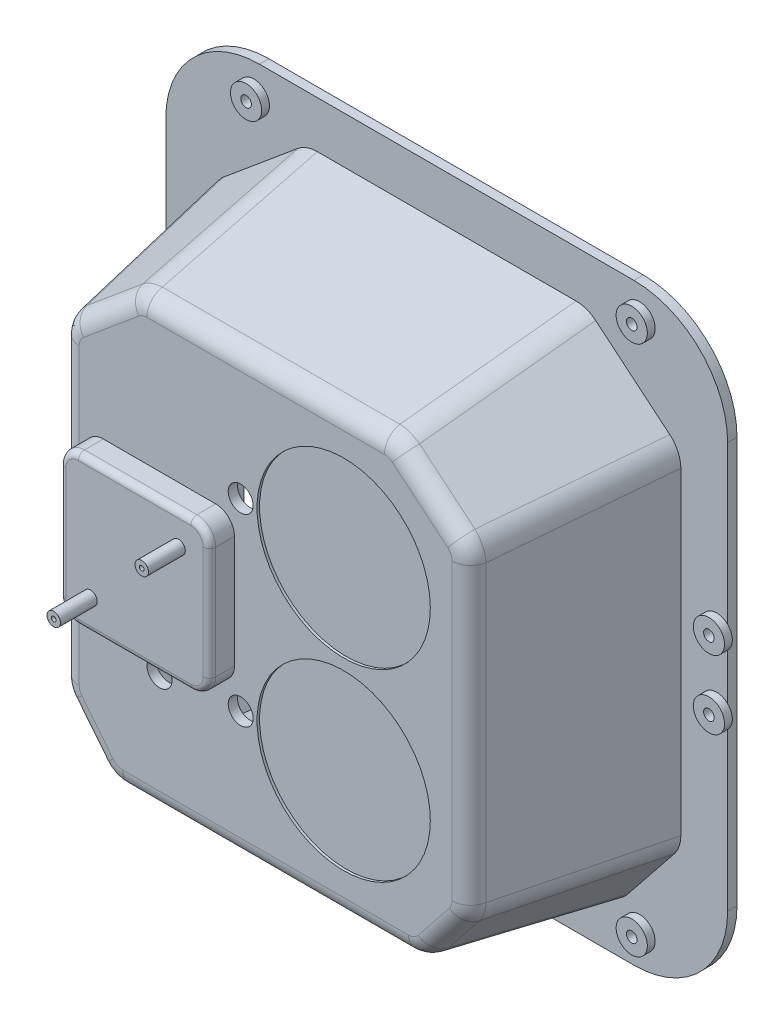
SolidWorks part; units mm, degrees
ref_plane "Front Plane" through (0, 0, 0) normal (0, 0, 1) x (1, 0, 0)
ref_plane "Top Plane" through (0, 0, 0) normal (0, 1, 0) x (1, 0, 0)
ref_plane "Right Plane" through (0, 0, 0) normal (1, 0, 0) x (0, 0, -1)
sketch "SK_Brim_180x190" plane through (0, 0, 0) normal (0, 0, 1) x (1, 0, 0)
  line L1 (-90, -95) -> (90, -95)
  line L2 (-90, -95) -> (-90, 95)
  line L3 (-90, 95) -> (90, 95)
  line L4 (90, -95) -> (90, 95)
  line L5 (-72, -77) -> (72, -77)
  line L6 (-72, -77) -> (-72, 77)
  line L7 (-72, 77) -> (72, 77)
  line L8 (72, -77) -> (72, 77)
extrude "Board_Mount_Brim_3mm" add sketch "SK_Brim_180x190" along normal blind 3
fillet "Brim_Outer_R30" radius 30 4 edges at (-90, 95, 1.5) (90, 95, 1.5) (90, -95, 1.5) (-90, -95, 1.5)
fillet "Brim_Inner_R10" radius 10 4 edges at (-72, 77, 1.5) (72, 77, 1.5) (72, -77, 1.5) (-72, -77, 1.5)
sketch "SK_Cockpit_Octagon" plane through (0, 0, 3) normal (0, 0, 1) x (1, 0, 0)
  line L0 (-55, -80) -> (55, -80)
  line L1 (55, -80) -> (75, -55)
  line L2 (75, -55) -> (75, 55)
  line L3 (75, 55) -> (45, 80)
  line L4 (45, 80) -> (-45, 80)
  line L5 (-45, 80) -> (-75, 55)
  line L6 (-75, 55) -> (-75, -55)
  line L7 (-75, -55) -> (-55, -80)
extrude "Cockpit_Canopy_Draft10deg" add sketch "SK_Cockpit_Octagon" along normal blind 58 draft 10
fillet "Canopy_Corners_R10" radius 10 8 edges at (-69.8865, -53.2063, 32) (-69.8865, 52.605, 32) (-43.1487, 74.8865, 32) (43.1487, 74.8865, 32) (69.8865, 52.605, 32) (69.8865, -53.2063, 32) (52.5423, -74.8865, 32) (-52.5423, -74.8865, 32)
fillet "Canopy_Roof_R6" radius 6 16 edges at (-57.8283, -60.0936, 61) (0, -69.773, 61) (57.8283, -60.0936, 61) (64.773, -1.1804, 61) (52.633, 60.3267, 61) (0, 69.773, 61) (-52.633, 60.3267, 61) (-64.773, -1.1804, 61) (-49.6183, -68.8027, 61) (49.6183, -68.8027, 61) (64.2184, -51.218, 61) (63.8447, 49.7752, 61) (41.0846, 69.1854, 61) (-41.0846, 69.1854, 61) (-63.8447, 49.7752, 61) (-64.2184, -51.218, 61)
sketch "SK_Symmetric_Cavity" plane through (0, 0, 0) normal (0, 0, -1) x (-1, 0, 0)
  line L0 (-53, -77) -> (53, -77)
  line L1 (57.3444, -77) -> (-57.3444, -77) construction
  line L2 (53, -77) -> (72, -52)
  line L3 (72, 57.4649) -> (72, -58.75) construction
  line L4 (72, -52) -> (72, 52)
  line L5 (72, 52) -> (43, 77)
  line L6 (-62, 77) -> (62, 77) construction
  line L7 (43, 77) -> (-43, 77)
  line L8 (-43, 77) -> (-72, 52)
  line L9 (-72, -67) -> (-72, 67) construction
  line L10 (-72, 52) -> (-72, -52)
  line L11 (-72, -52) -> (-53, -77)
extrude "Symmetric_Electronics_Cavity_58H" cut sketch "SK_Symmetric_Cavity" against normal blind 58 draft 10
sketch "Sketch7" plane through (0, 0, 61) normal (0, 0, 1) x (1, 0, 0)
  circle A0 centre (25, -29.5) radius 28.5
  circle A1 centre (25, 29.5) radius 28.5
extrude "Boss-Extrude4" add sketch "Sketch7" along normal blind 1.5
sketch "Sketch8" plane through (0, 0, 62.5) normal (0, 0, 1) x (1, 0, 0)
  circle A0 centre (25, -29.5) radius 28.5
  circle A1 centre (25, 29.5) radius 28.5
extrude "Cut-Extrude4" cut sketch "Sketch8" against normal blind 1.5
sketch "Sketch12" plane through (0, 0, 61) normal (0, 0, 1) x (1, 0, 0)
  circle A0 centre (25, -29.5) radius 27.75
extrude "Cut-Extrude8" cut sketch "Sketch12" against normal blind 0.8
sketch "Sketch13" plane through (0, 0, 61) normal (0, 0, 1) x (1, 0, 0)
  circle A0 centre (25, 29.5) radius 27.75
extrude "Cut-Extrude9" cut sketch "Sketch13" against normal blind 0.8
sketch "Sketch14" plane through (0, 0, 61) normal (0, 0, 1) x (1, 0, 0)
  line L1 (-58, -24) -> (-10, -24)
  line L2 (-58, -24) -> (-58, 24)
  line L3 (-58, 24) -> (-10, 24)
  line L4 (-10, -24) -> (-10, 24)
extrude "Boss-Extrude5" add sketch "Sketch14" along normal blind 8
fillet "Fillet3" radius 6 4 edges at (-58, 24, 65) (-10, 24, 65) (-10, -24, 65) (-58, -24, 65)
fillet "Fillet4" radius 2 8 edges at (-58, 0, 69) (-34, -24, 69) (-10, 0, 69) (-34, 24, 69) (-56.2426, -22.2426, 69) (-11.7574, -22.2426, 69) (-11.7574, 22.2426, 69) (-56.2426, 22.2426, 69)
sketch "Sketch15" plane through (0, 0, 69) normal (0, 0, 1) x (1, 0, 0)
  circle A0 centre (-48.1, -14.1) radius 2.15
  circle A1 centre (-19.9, 14.1) radius 2.15
extrude "Boss-Extrude6" add sketch "Sketch15" along normal blind 11.8
sketch "Sketch16" plane through (0, 0, 80.8) normal (0, 0, 1) x (1, 0, 0)
  circle A0 centre (-48.1, -14.1) radius 0.75
  circle A1 centre (-19.9, 14.1) radius 0.75
extrude "Cut-Extrude10" cut sketch "Sketch16" against normal blind 11.3
sketch "Sketch17" plane through (0, 0, 61) normal (0, 0, 1) x (1, 0, 0)
  circle A0 centre (-8, -29.5) radius 4
  circle A1 centre (-8, 29.5) radius 4
extrude "Cut-Extrude11" cut sketch "Sketch17" against normal blind 4
sketch "Sketch18" plane through (0, 0, 61) normal (0, 0, 1) x (1, 0, 0)
  circle A0 centre (-34, -32) radius 4
extrude "Cut-Extrude12" cut sketch "Sketch18" against normal blind 4
sketch "Sketch19" plane through (0, 0, 0) normal (0, 0, 1) x (1, 0, 0)
  line L0 (-50, -73) -> (50, -73)
  line L1 (-72, -77) -> (72, -77)
  line L2 (-72, -77) -> (-72, 77)
  line L3 (-72, 77) -> (72, 77)
  line L4 (72, -77) -> (72, 77)
  line L5 (50, -73) -> (68, -50)
  line L6 (68, -50) -> (68, 50)
  line L7 (68, 50) -> (40, 73)
  line L8 (40, 73) -> (-40, 73)
  line L9 (-40, 73) -> (-68, 50)
  line L10 (-68, 50) -> (-68, -50)
  line L11 (-68, -50) -> (-50, -73)
extrude "Boss-Extrude7" add sketch "Sketch19" along normal blind 3
sketch "Sketch20" plane through (0, 0, 3) normal (0, 0, 1) x (1, 0, 0)
  circle A0 centre (-86.5, -11) radius 1.7
  circle A1 centre (-86.5, 11) radius 1.7
  circle A2 centre (86.5, -11) radius 1.7
  circle A3 centre (86.5, 11) radius 1.7
  circle A4 centre (-61.7761, -84.9997) radius 1.7
  circle A5 centre (61.7761, -84.9997) radius 1.7
  circle A6 centre (-61.7761, 84.9997) radius 1.7
  circle A7 centre (61.7761, 84.9997) radius 1.7
extrude "Cut-Extrude13" cut sketch "Sketch20" against normal blind 3.2
sketch "Sketch21" plane through (0, 0, 3) normal (0, 0, 1) x (1, 0, 0)
  circle A0 centre (-86.5, -11) radius 5
  circle A1 centre (-86.5, -11) radius 1.7
  circle A2 centre (-86.5, 11) radius 5
  circle A3 centre (-86.5, 11) radius 1.7
  circle A4 centre (86.5, -11) radius 5
  circle A5 centre (86.5, -11) radius 1.7
  circle A6 centre (86.5, 11) radius 5
  circle A7 centre (86.5, 11) radius 1.7
  circle A8 centre (-61.7761, -84.9997) radius 5
  circle A9 centre (-61.7761, -84.9997) radius 1.7
  circle A10 centre (61.7761, -84.9997) radius 5
  circle A11 centre (61.7761, -84.9997) radius 1.7
  circle A12 centre (-61.7761, 84.9997) radius 5
  circle A13 centre (-61.7761, 84.9997) radius 1.7
  circle A14 centre (61.7761, 84.9997) radius 5
  circle A15 centre (61.7761, 84.9997) radius 1.7
extrude "Boss-Extrude8" add sketch "Sketch21" along normal blind 2.5
